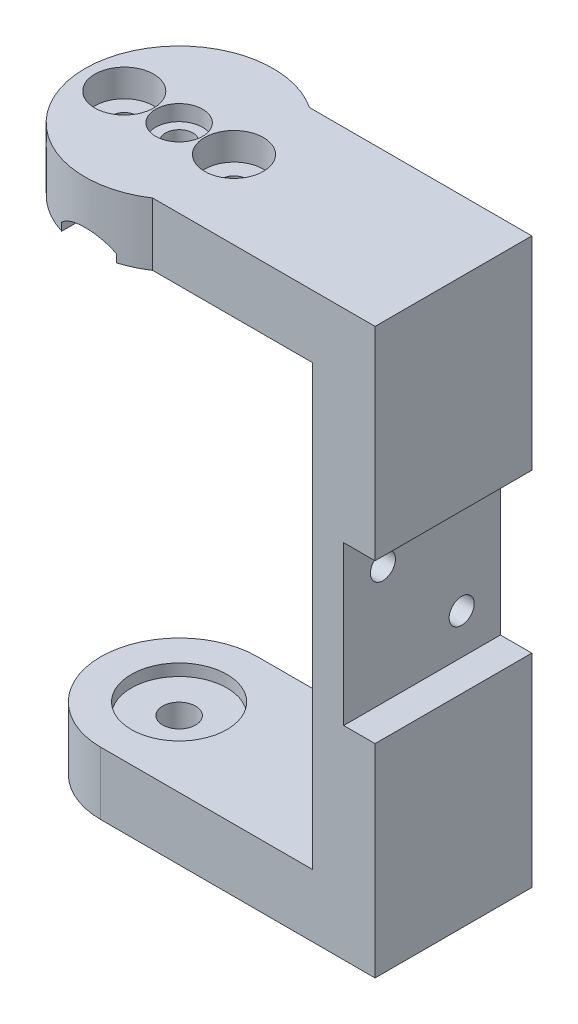
SolidWorks part; units mm, degrees
material "ABS"
ref_plane "Płaszczyzna przednia" through (0, 0, 0) normal (0, 0, 1) x (1, 0, 0)
ref_plane "Płaszczyzna górna" through (0, 0, 0) normal (0, 1, 0) x (1, 0, 0)
ref_plane "Płaszczyzna prawa" through (0, 0, 0) normal (1, 0, 0) x (0, 0, -1)
sketch "Szkic1" plane through (0, 0, 0) normal (0, 1, 0) x (1, 0, 0)
  line L1 (-10, 10) -> (35, 10)
  line L2 (-10, 10) -> (-10, -10)
  line L3 (-10, -10) -> (35, -10)
  line L4 (35, 10) -> (35, -10)
  line L5 (-55, 0) -> (55, 0) construction
  line L6 (0, 0) -> (12.6728, 0) construction
  circle A0 centre (0, 0) radius 2.1
  dimension "D1" = 4.2
  dimension "D4" = 10
  dimension "D2" = 20
  dimension "D3" = 45
extrude "Dodanie-wyciągnięcie1" add sketch "Szkic1" along normal blind 8
sketch "Szkic2" plane through (0, 8, 0) normal (0, 1, 0) x (1, 0, 0)
  circle A0 centre (0, 0) radius 6.1
  dimension "D1" = 12.2
extrude "Wytnij-wyciągnięcie1" cut sketch "Szkic2" against normal blind 1.5
sketch "Szkic3" plane through (0, 0, 0) normal (0, -1, 0) x (1, 0, 0)
  circle A0 centre (0, 0) radius 6.1
  dimension "D1" = 12.2
extrude "Wytnij-wyciągnięcie2" cut sketch "Szkic3" against normal blind 1.5
sketch "Szkic4" plane through (0, 8, 0) normal (0, 1, 0) x (1, 0, 0)
  line L0 (-10, -10) -> (35, -10) construction
  line L1 (35, 10) -> (27, 10)
  line L2 (35, 10) -> (35, -10)
  line L3 (35, -10) -> (27, -10)
  line L4 (27, 10) -> (27, -10)
  dimension "D1" = 8
extrude "Dodanie-wyciągnięcie2" add sketch "Szkic4" along normal blind 56
fillet "Zaokrąglenie1" radius 10 2 edges at (-10, 4, -10) (-10, 4, 10)
sketch "Szkic5" plane through (0, 64, 0) normal (0, 1, 0) x (1, 0, 0)
  line L3 (35, 10) -> (35, -10)
  line L4 (35, 10) -> (6.6332, 10)
  line L5 (35, -10) -> (6.6332, -10)
  arc A1 (6.6332, 10) -> (6.6332, -10) centre (0, 0) ccw
  dimension "D1" = 24
extrude "Dodanie-wyciągnięcie3" add sketch "Szkic5" along normal blind 8 contours L3 L5 A1 L4
sketch "Szkic6" plane through (0, 72, 0) normal (0, 1, 0) x (1, 0, 0)
  line L2 (-4.4, 0) -> (4.4, 0) construction
  line L3 (0, -4.4) -> (0, 4.4) construction
  circle A2 centre (-7, 0) radius 1.6
  circle A3 centre (7, 0) radius 1.6
  point P11 (0.0979, -0.4093)
  dimension "D1" = 3.2
  dimension "D2" = 7
extrude "Wytnij-wyciągnięcie3" cut sketch "Szkic6" against normal up to next
sketch "Szkic7" plane through (0, 72, 0) normal (0, 1, 0) x (1, 0, 0)
  circle A0 centre (7, 0) radius 3.75
  circle A1 centre (-7, 0) radius 3.75
  dimension "D1" = 7.5
  dimension "D2" = 7.5
extrude "Wytnij-wyciągnięcie4" cut sketch "Szkic7" against normal blind 3.5
ref_plane "Płaszczyzna1" through (0, 0, 12) normal (0, 0, 1) x (1, 0, 0)
sketch "Szkic9" plane through (0, 0, 12) normal (0, 0, 1) x (1, 0, 0)
  line L0 (-3.5, 64) -> (3.5, 64)
  line L1 (-3.5, 64) -> (-3.5, 65)
  line L2 (3.5, 64) -> (3.5, 65)
  line L4 (-12, 64) -> (6.6332, 64) construction
  line L5 (0, -4.4) -> (0, 4.4) construction
  line L6 (0, 70.0564) -> (0, 58.6294) construction
  arc A0 (3.5, 65) -> (-3.5, 65) centre (0, 61.4293) ccw
  dimension "D3" = 5
  dimension "D1" = 1
  dimension "D2" = 3.5
extrude "Wytnij-wyciągnięcie5" cut sketch "Szkic9" against normal up to next
sketch "Szkic10" plane through (0, 72, 0) normal (0, 1, 0) x (1, 0, 0)
  circle A0 centre (0, 0) radius 3
  dimension "D1" = 6
extrude "Wytnij-wyciągnięcie6" cut sketch "Szkic10" against normal blind 2
sketch "Szkic11" plane through (0, 70, 0) normal (0, 1, 0) x (1, 0, 0)
  circle A0 centre (0, 0) radius 1.75
  dimension "D1" = 3.5
extrude "Wytnij-wyciągnięcie7" cut sketch "Szkic11" against normal up to next
ref_plane "Płaszczyzna2" through (0, 36, 0) normal (0, 1, 0) x (1, 0, 0)
sketch "Szkic12" plane through (35, 0, 0) normal (1, 0, 0) x (0, 0, -1)
  line L0 (-10, 72) -> (-10, 0) construction
  line L1 (10, 72) -> (10, 0) construction
  line L2 (-10, 46.1) -> (10, 46.1)
  line L3 (-10, 46.1) -> (-10, 25.9)
  line L4 (-10, 25.9) -> (10, 25.9)
  line L5 (10, 46.1) -> (10, 25.9)
  line L6 (13.2, 36) -> (-13.2, 36) construction
  line L7 (-10, 36) -> (10, 36) construction
  dimension "D1" = 20.2
extrude "Wytnij-wyciągnięcie8" cut sketch "Szkic12" against normal blind 4
sketch "Szkic13" plane through (31, 0, 0) normal (1, 0, 0) x (0, 0, -1)
  line L2 (10, 46.1) -> (-10, 25.9) construction
  line L3 (13.2, 36) -> (-13.2, 36) construction
  line L4 (0, 4.4) -> (0, -4.4) construction
  circle A0 centre (-5, 41) radius 1.6
  circle A1 centre (5.0495, 31.05) radius 1.6
  dimension "D1" = 3.2
  dimension "D3" = 5
  dimension "D2" = 5
extrude "Wytnij-wyciągnięcie9" cut sketch "Szkic13" against normal up to next
sketch "Szkic14" plane through (27, 0, 0) normal (-1, 0, 0) x (0, 0, 1)
  circle A0 centre (5, 41) radius 3.75
  circle A1 centre (-5.0495, 31.05) radius 3.75
  dimension "D1" = 7.5
extrude "Wytnij-wyciągnięcie10" cut sketch "Szkic14" against normal blind 1
